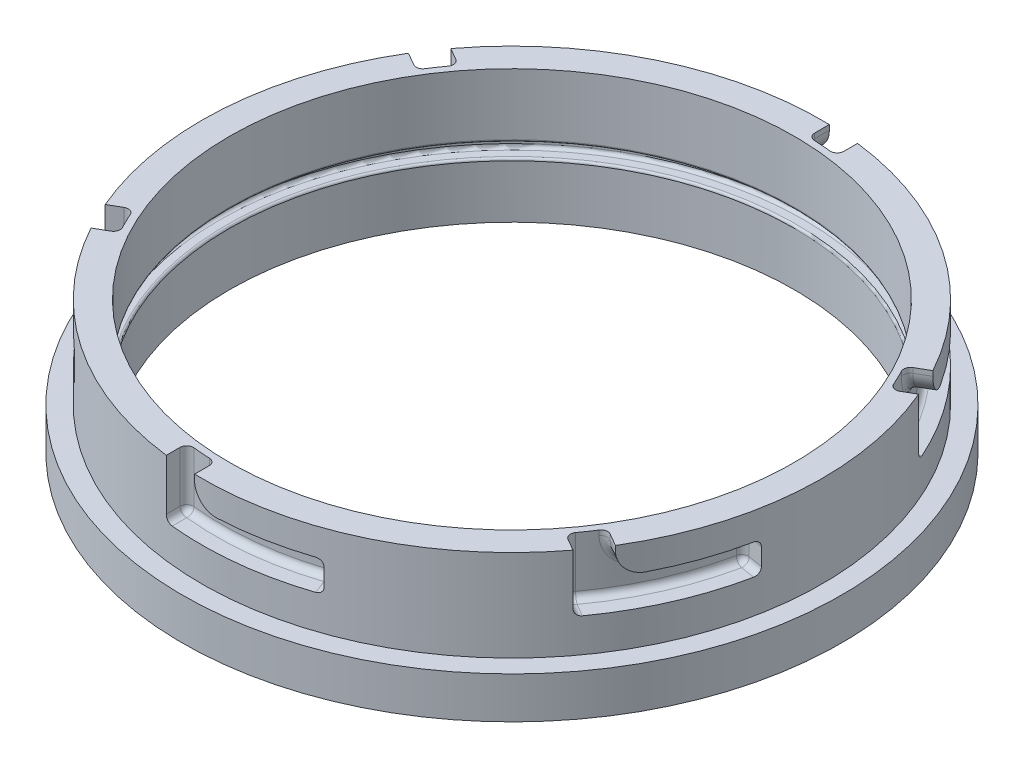
SolidWorks part; units mm, degrees
material "6061-T6 (SS)"
ref_plane "Front Plane" through (0, 0, 0) normal (0, 0, 1) x (1, 0, 0)
ref_plane "Top Plane" through (0, 0, 0) normal (0, 1, 0) x (1, 0, 0)
ref_plane "Right Plane" through (0, 0, 0) normal (1, 0, 0) x (0, 0, -1)
sketch "Sketch1" plane through (0, 0, 0) normal (0, 0, 1) x (1, 0, 0)
  line L0 (0, 60.758) -> (0, -61.3352) construction
  line L1 (71.12, 36.5125) -> (71.12, 15.5575)
  line L2 (71.12, 15.5575) -> (75.565, 15.5575)
  line L3 (75.565, 15.5575) -> (75.565, 6.0325)
  line L4 (75.565, 6.0325) -> (64.77, 6.0325)
  line L5 (64.77, 6.0325) -> (64.77, 18.7325)
  line L6 (64.77, 36.5125) -> (71.12, 36.5125)
  line L7 (64.77, 18.7325) -> (67.818, 18.7325)
  line L8 (67.818, 18.7325) -> (67.818, 21.9075)
  line L9 (67.818, 21.9075) -> (64.77, 21.9075)
  line L10 (64.77, 21.9075) -> (64.77, 36.5125)
  dimension "D1" = 6.35
  dimension "D2" = 9.525
  dimension "D3" = 30.48
  dimension "D4" = 71.12
  dimension "D5" = 75.565
  dimension "D6" = 3.048
  dimension "D7" = 12.7
  dimension "D8" = 15.875
revolve "Revolve1" add sketch "Sketch1" angle 360 about L0
sketch "Sketch2" plane through (0, 36.5125, 0) normal (0, 1, 0) x (1, 0, 0)
  line L0 (-8.6592, -70.5909) -> (-8.6592, -65.726)
  line L1 (-1.6742, -71.1003) -> (-1.6742, -66.2729)
  arc A0 (-1.6742, -71.1003) -> (-8.6592, -70.5909) centre (0, 0) cw
  circle A1 centre (0, 0) radius 71.12 construction
  arc A2 (-1.6742, -66.2729) -> (-8.6592, -65.726) centre (0, 0) cw
  dimension "D1" = 4.826
  dimension "D2" = 6.985
  dimension "D3" = 6.985
extrude "Cut-Extrude1" cut sketch "Sketch2" against normal blind 13.208
sketch "Sketch10" plane through (-1.6742, 0, 0) normal (-1, 0, 0) x (0, 0, 1)
  line L0 (66.2729, 23.3045) -> (66.2729, 30.2895)
  line L1 (66.2729, 23.3045) -> (66.2729, 36.5125) construction
  line L2 (66.2729, 30.2895) -> (71.1003, 30.2895)
  line L3 (71.1003, 23.3045) -> (71.1003, 36.5125) construction
  line L4 (71.1003, 30.2895) -> (71.1003, 23.3045)
  line L5 (71.1003, 23.3045) -> (66.2729, 23.3045)
  dimension "D1" = 6.985
ref_axis "Axis1" through (0, 6.0325, 0) along (0, 1, 0)
sketch "Sketch21" plane through (0, 23.3045, 0) normal (0, 1, 0) x (1, 0, 0)
  line L0 (-1.6742, -71.1003) -> (-1.6742, -66.2729) construction
  arc A0 (-1.6742, -73.5126) -> (73.4476, -3.5158) centre (0, 0) ccw
sketch "Sketch22" plane through (0, 23.3045, 0) normal (0, 1, 0) x (1, 0, 0)
  circle A1 centre (0, 0) radius 73.5317
sketch "Sketch23" plane through (0, 23.3045, 0) normal (0, 1, 0) x (1, 0, 0)
  arc A0 (-1.6742, -71.1003) -> (23.922, -66.9761) centre (0, 0) ccw
sweep "Cut-Sweep2" cut profiles "Sketch10" path "Sketch23"
fillet "Fillet1" radius 5.08 1 edges at (-1.6742, 30.2895, 68.6866)
fillet "Fillet7" radius 1.524 9 edges at (-1.6742, 35.941, 66.2729) (0.2383, 31.3979, 66.2936) (23.0569, 23.3045, 64.7227) (-8.6592, 23.3045, 68.1585) (23.0569, 30.2895, 64.7227) (22.1917, 26.797, 62.4694) (12.9344, 30.2895, 65.02) (6.9594, 23.3045, 65.9277) (-8.6592, 29.9085, 65.726)
pattern_circular "CirPattern1" count 6 over 360 about axis through (0, 60.758, 0) along (0, 1, 0) of "Fillet1", "Cut-Extrude1", "Cut-Sweep2", "Fillet7" reverse direction yes
fillet "Fillet2" radius 0.762 2 edges at (-67.818, 21.9075, 0) (-67.818, 18.7325, 0)
fillet "Fillet3" radius 0.508 2 edges at (-64.77, 18.7325, 0) (-64.77, 21.9075, 0)
sketch "Sketch24" plane through (0, 6.0325, 0) normal (0, -1, 0) x (1, 0, 0)
  line L0 (-2.0961, 67.1054) -> (-1.1566, 67.1033)
  line L1 (-1.6263, 67.1043) -> (-1.6325, 64.2837) construction
  line L2 (-3.1931, 64.513) -> (-0.071, 64.5062)
  spline S0 degree 3 poles (-2.0961, 67.1054) (-2.1672, 66.9295) (-2.2659, 66.6682) (-2.4002, 66.2739) (-2.4676, 66.0573) (-2.5063, 65.9255) knots 0 0 0 0 0.455486 0.670301 1 1 1 1
  spline S1 degree 3 poles (-2.5063, 65.9255) (-2.5773, 65.6449) (-2.6547, 65.2845) (-2.7636, 64.9081) (-2.7851, 64.7854) (-2.8051, 64.7157) (-2.8445, 64.6485) (-2.9065, 64.5845) (-3.0202, 64.5178) (-3.1269, 64.5162) (-3.1931, 64.513) knots 0 0 0 0 0.50758 0.647219 0.68628 0.726157 0.773713 0.821128 0.881401 1 1 1 1
  spline S2 degree 3 poles (-1.1566, 67.1033) (-1.0863, 66.9271) (-0.9887, 66.6654) (-0.8561, 66.2705) (-0.7897, 66.0536) (-0.7516, 65.9217) knots 0 0 0 0 0.455486 0.670301 1 1 1 1
  spline S3 degree 3 poles (-0.7516, 65.9217) (-0.6962, 65.7094) (-0.6454, 65.4407) (-0.5548, 65.1173) (-0.5157, 64.9486) (-0.4854, 64.8115) (-0.4614, 64.7227) (-0.4366, 64.6731) (-0.4076, 64.6316) (-0.3644, 64.5877) (-0.3091, 64.5493) (-0.2095, 64.5089) (-0.1255, 64.5109) (-0.071, 64.5062) knots 0 0 0 0 0.384807 0.478666 0.588978 0.688379 0.725395 0.749588 0.785292 0.813657 0.857185 0.902571 1 1 1 1
extrude "Cut-Extrude3" [suppressed] cut sketch "Sketch24" against normal blind 13.208
fillet "Fillet5" [suppressed] radius 0.508 tangent propagation no
fillet "Fillet6" [suppressed] radius 0.254
pattern_circular "CirPattern3" [suppressed] count 120 every 3 of bodies 114
